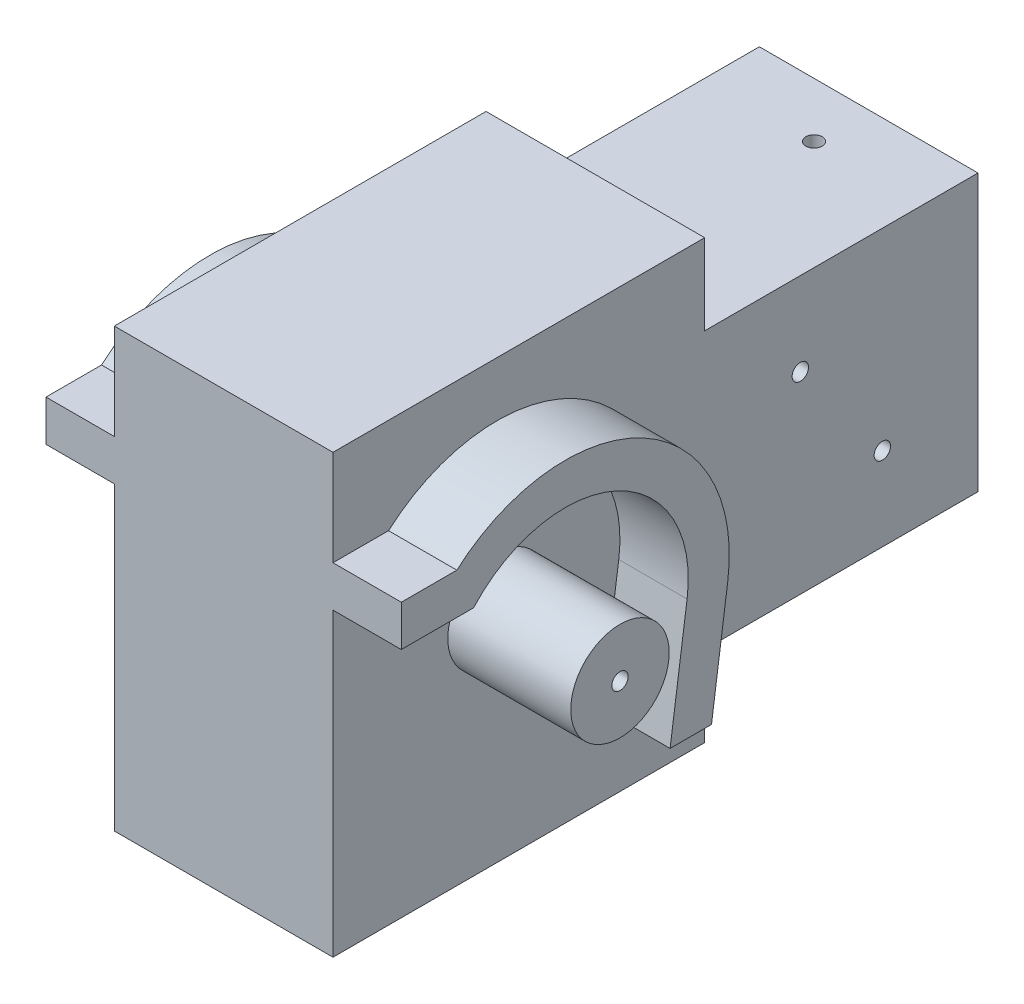
SolidWorks part; units mm, degrees
ref_plane "前视基准面" through (0, 0, 0) normal (0, 0, 1) x (1, 0, 0)
ref_plane "上视基准面" through (0, 0, 0) normal (0, 1, 0) x (1, 0, 0)
ref_plane "右视基准面" through (0, 0, 0) normal (1, 0, 0) x (0, 0, -1)
other "Configuration Table"
sketch "草图2" plane through (0, 0, 0) normal (1, 0, 0) x (0, 0, -1)
  line L0 (-6, 0) -> (17.6, 0) construction
  line L1 (-6, 8) -> (17.6, 8)
  line L2 (-6, 8) -> (-6, -8)
  line L3 (-6, -8) -> (17.6, -8)
  line L4 (17.6, 8) -> (17.6, -8)
  line L5 (1.8, 8) -> (1.8, -8)
  line L6 (4.4562, -0.6263) -> (3.4199, -8)
  line L7 (0, -4.5) -> (-6, -4.5)
  line L8 (0, -4.5) -> (0, 3)
  line L9 (0, 3) -> (-6, 3)
  line L10 (-6, -4.5) -> (-6, 3)
  line L12 (0, 4.5) -> (-6, 4.5)
  line L13 (4.9346, -8) -> (5.9416, -0.835)
  line L14 (0, 5) -> (17.6, 5)
  line L15 (0, 5) -> (0, -5)
  line L16 (0, -5) -> (17.6, -5)
  line L17 (17.6, 5) -> (17.6, -5)
  circle A0 centre (0, 0) radius 1.8
  circle A1 centre (0, 0) radius 4.5
  circle A2 centre (0, 0) radius 6
  dimension "D1" = 3.6
  dimension "D3" = 9
  dimension "D7" = 10
  dimension "D2" = 7.5
  dimension "D4" = 6
  dimension "D5" = 16
  dimension "D6" = 15.8
  dimension "D8" = 82
extrude "凸台-拉伸1" add sketch "草图2" along normal blind 4 contours L1 L4 L3 L2
extrude "凸台-拉伸3" add sketch "草图2<10>" along normal blind 4.5 from surface contours A0 L0 L8 | L8 L0 A0 | L0 L15 A0 | L0 A0 L15 region at (0, -0.7639, -0.7639) region at (0, 0.7639, -0.7639) region at (0, -0.7639, 0.7639) region at (0, 0.7639, 0.7639) starting at face at (4, 0, -5.8)
sketch "草图2<10>" plane through (0, 0, 0) normal (1, 0, 0) x (0, 0, -1) same geometry as "草图2"
sketch "草图5" plane through (8.5, 0, 0) normal (1, 0, 0) x (0, 0, -1)
  circle A0 centre (0, 0) radius 0.3
  dimension "D1" = 0.6
extrude "切除-拉伸10" cut sketch "草图5" against normal blind 1
extrude "凸台-拉伸2" add sketch "草图2<4>" along normal blind 2.5 from surface contours L12 A2 L9 A1 | L5 A2 L12 L15 L14 | A1 L5 L14 L15 | A1 L0 A2 L14 L5 | L14 A2 L5 | L0 A1 L6 A2 | A2 L6 L16 L13 | L16 L6 L3 L13 | A2 L12 L2 L9 region at (0, 2.6915, -4.1879) region at (0, -1.8211, -4.9358) region at (0, 4.6785, -0.9896) region at (0, 5.2074, 0.838) region at (0, 5.2565, -2.3339) region at (0, 3.8249, 3.3838) region at (0, -3.9797, -4.9725) region at (0, 3.8627, 5.2791) region at (0, -6.5, -4.3881) starting at face at (4, 0, -1.8)
sketch "草图2<4>" plane through (0, 0, 0) normal (1, 0, 0) x (0, 0, -1) same geometry as "草图2"
sketch "草图6" plane through (0, 0, -17.6) normal (0, 0, -1) x (-1, 0, 0)
  line L0 (-4, 6) -> (-4, -0.835) construction
  line L1 (0, 8) -> (-4, 8)
  line L2 (0, 8) -> (0, 5.05)
  line L3 (0, 5.05) -> (-4, 5.05)
  line L4 (-4, 8) -> (-4, 5.05)
  line L5 (-4, -0.835) -> (-4, -8) construction
  line L6 (0, -8) -> (-4, -8)
  line L7 (0, -8) -> (0, -5.05)
  line L8 (0, -5.05) -> (-4, -5.05)
  line L9 (-4, -8) -> (-4, -5.05)
  dimension "D1" = 10.1
extrude "切除-拉伸11" cut sketch "草图6" against normal blind 10
sketch "草图7" plane through (0, -5.05, 0) normal (0, -1, 0) x (1, 0, 0)
  line L0 (0, -7.6) -> (0, -17.6) construction
  line L4 (0, -17.6) -> (4, -17.6) construction
  line L5 (4, -7.6) -> (0, -7.6) construction
  circle A0 centre (0, -9.6) radius 0.3
  circle A1 centre (0, -15.6) radius 0.3
  dimension "D1" = 0.6
  dimension "D2" = 2
  dimension "D3" = 2
extrude "切除-拉伸12" cut sketch "草图7" against normal through all
sketch "草图8" plane through (6.5, 0, 0) normal (1, 0, 0) x (0, 0, -1)
  line L0 (7.6, -5.05) -> (17.6, -5.05) construction
  line L1 (7.6, -5.05) -> (-6, -5.05)
  line L2 (7.6, -5.05) -> (7.6, -8)
  line L3 (7.6, -8) -> (-6, -8)
  line L4 (-6, -5.05) -> (-6, -8)
  line L5 (7.6, -5.05) -> (7.6, -8) construction
extrude "切除-拉伸13" cut sketch "草图8" against normal up to surface (2.5 mm away) up to face at (4, 0, -1.8)
mirror "镜向1" about plane through (0, 0, 0) normal (1, 0, 0) of bodies 125 107
sketch "草图9" plane through (-4, 0, 0) normal (-1, 0, 0) x (0, 0, 1)
  circle A0 centre (-14.1, -2) radius 0.3
  circle A1 centre (-11.1, 2) radius 0.3
  point P6 (0, 0)
  point P7 (0, 0)
  point P8 (0, 0)
  dimension "D1" = 0.6
extrude "切除-拉伸14" cut sketch "草图9" against normal up to next contours A0 | A1
